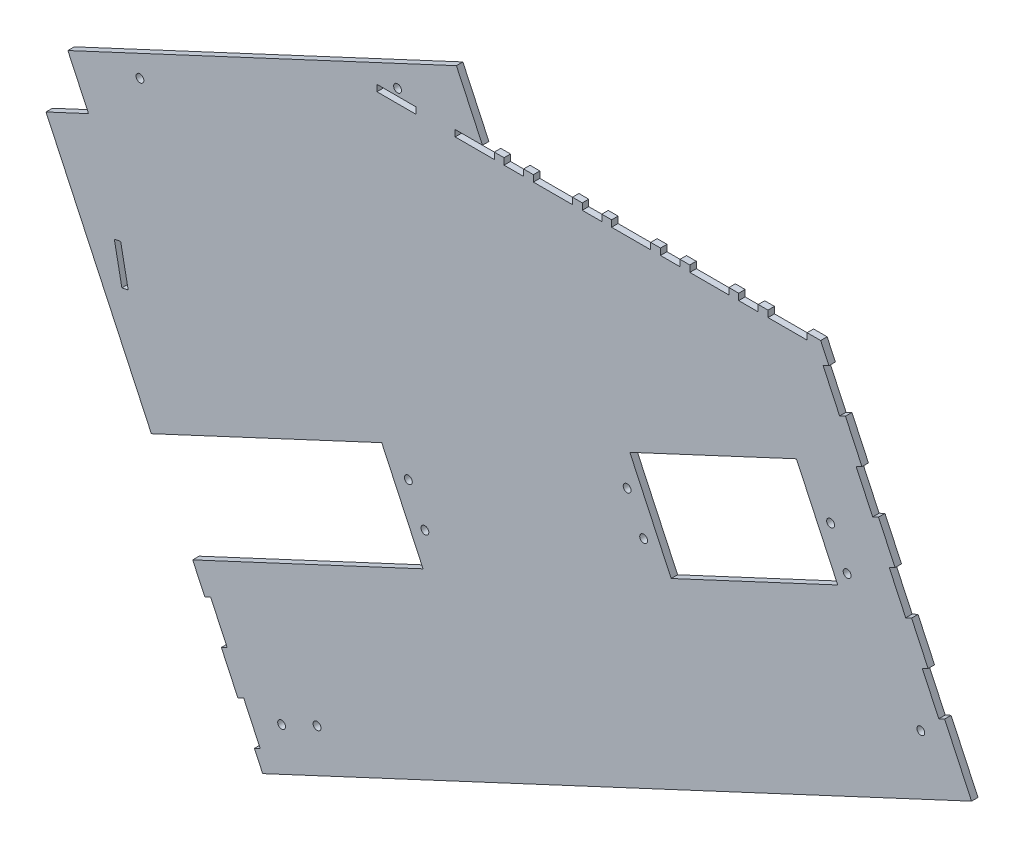
SolidWorks part; units mm, degrees
material "Balsa"
ref_plane "Front Plane" through (0, 0, 0) normal (0, 0, 1) x (1, 0, 0)
ref_plane "Top Plane" through (0, 0, 0) normal (0, 1, 0) x (1, 0, 0)
ref_plane "Right Plane" through (0, 0, 0) normal (1, 0, 0) x (0, 0, -1)
sketch "Sketch1" plane through (0, 0, 0) normal (0, 0, 1) x (1, 0, 0)
  line L0 (321.5462, 12.6346) -> (148.586, 12.6346)
  line L1 (148.586, 12.6346) -> (135.2566, 41.2196)
  line L2 (135.2566, 41.2196) -> (-63.4467, -51.4373)
  line L3 (-63.4467, -51.4373) -> (57.9293, -311.7289) construction
  line L4 (57.9293, -311.7289) -> (398.701, -152.8244)
  line L5 (271.5352, 119.8836) -> (277.3251, 107.4672) construction
  line L6 (190.5834, 136.311) -> (-12.0446, 41.824) construction
  line L7 (-63.4467, -51.4373) -> (255.5737, 97.3243) construction
  line L8 (398.701, -152.8244) -> (321.5462, 12.6346)
  line L9 (57.9293, -311.7289) -> (36.1779, -321.8717)
  line L10 (36.1779, -321.8717) -> (-74.6326, -84.2378)
  line L12 (-74.6326, -84.2378) -> (-52.8812, -74.095)
  line L13 (-90.9879, -49.1637) -> (-85.1981, -61.5801) construction
  line L14 (-52.8812, -74.095) -> (-63.4467, -51.4373)
  line L15 (73.956, 12.6346) -> (94.6178, 12.6346) construction
  line L19 (148.586, 12.6346) -> (135.2566, 41.2196) construction
  circle A0 centre (162.7613, -40.6644) radius 32.5 construction
  circle A1 centre (336.0773, -108.8767) radius 32.5 construction
  circle A2 centre (90.1802, -40.6644) radius 32.5 construction
  circle A3 centre (232.5481, -40.6644) radius 32.5 construction
  circle A4 centre (207.2768, 100.5118) radius 39.5 construction
  arc A5 (-3.3339, 41.4724) -> (-17.3744, 34.9252) centre (-8.0297, 33.2141) ccw construction
  circle A6 centre (304.5287, -40.6644) radius 32.5 construction
  circle A7 centre (254.9584, -108.8767) radius 32.5 construction
  circle A8 centre (179.3206, -108.8767) radius 32.5 construction
  circle A9 centre (101.4264, -108.8767) radius 32.5 construction
  circle A10 centre (270.383, -163.8108) radius 32.5 construction
  circle A11 centre (372.7594, -134.5783) radius 2
  dimension "D2" = 65
  dimension "D3" = 65
  dimension "D5" = 4
  dimension "D1" = 350
  dimension "D4" = 25
  dimension "24.5/2" = 15.8
  dimension "D6" = 27.5
extrude "Boss-Extrude1" add sketch "Sketch1" along normal up to surface (3.3 mm away)
sketch "Sketch2" plane through (0, 0, 3.3) normal (0, 0, 1) x (1, 0, 0)
  circle A0 centre (105.1447, 16.1444) radius 2
  circle A1 centre (-26.5934, -45.2861) radius 2
  circle A2 centre (-26.5934, -45.2861) radius 2 construction
  circle A3 centre (105.1447, 16.1444) radius 2 construction
extrude "Cut-Extrude1" cut sketch "Sketch2" against normal through all
sketch "Sketch3" plane through (0, 0, 3.3) normal (0, 0, 1) x (1, 0, 0)
  line L2 (398.701, -152.8244) -> (36.1779, -321.8717) construction
  line L3 (36.1779, -321.8717) -> (-74.6326, -84.2378) construction
  circle A0 centre (45.8517, -295.2932) radius 2
  circle A1 centre (63.9779, -286.8408) radius 2
  dimension "D1" = 4
  dimension "D2" = 4
  dimension "D3" = 20
  dimension "D5" = 20
  dimension "D6" = 20
  dimension "D4" = 20
extrude "Cut-Extrude2" cut sketch "Sketch3" against normal blind 4
sketch "Sketch4" plane through (0, 0, 3.3) normal (0, 0, 1) x (1, 0, 0)
  line L0 (330.2782, -91.2744) -> (309.1473, -45.959)
  line L1 (309.1473, -45.959) -> (223.9543, -85.6851)
  line L2 (223.9543, -85.6851) -> (245.0853, -131.0005)
  line L3 (245.0853, -131.0005) -> (330.2782, -91.2744)
  line L4 (309.1473, -45.959) -> (223.9543, -85.6851) construction
  line L5 (245.0853, -131.0005) -> (330.2782, -91.2744) construction
  line L6 (330.2782, -91.2744) -> (309.1473, -45.959) construction
  line L7 (118.2022, -190.1671) -> (97.0712, -144.8517)
  line L8 (97.0712, -144.8517) -> (-20.7488, -199.7921)
  line L9 (-20.7488, -199.7921) -> (0.3821, -245.1075)
  line L10 (0.3821, -245.1075) -> (118.2022, -190.1671)
  line L11 (118.2022, -190.1671) -> (0.3821, -245.1075) construction
  line L12 (-20.7488, -199.7921) -> (97.0712, -144.8517) construction
  line L13 (97.0712, -144.8517) -> (118.2022, -190.1671) construction
extrude "Cut-Extrude3" cut sketch "Sketch4" against normal blind 10
sketch "Sketch5" plane through (0, 0, 3.3) normal (0, 0, 1) x (1, 0, 0)
  circle A0 centre (231.009, -120.4069) radius 2
  circle A1 centre (222.5566, -102.2807) radius 2
  circle A2 centre (119.135, -172.5746) radius 2
  circle A3 centre (110.6826, -154.4484) radius 2
  circle A4 centre (119.135, -172.5746) radius 2 construction
  circle A7 centre (110.6826, -154.4484) radius 2 construction
  circle A8 centre (222.5566, -102.2807) radius 2 construction
  circle A9 centre (231.009, -120.4069) radius 2 construction
extrude "Cut-Extrude4" cut sketch "Sketch5" against normal blind 10
sketch "Sketch6" plane through (0, 0, 3.3) normal (0, 0, 1) x (1, 0, 0)
  line L0 (148.586, 12.6346) -> (321.5462, 12.6346) construction
  line L1 (314.6178, 12.6346) -> (294.6178, 12.6346)
  line L2 (314.6178, 12.6346) -> (314.6178, 9.3346)
  line L3 (314.6178, 9.3346) -> (294.6178, 9.3346)
  line L4 (294.6178, 12.6346) -> (294.6178, 9.3346)
  line L5 (314.6178, 12.6346) -> (294.6178, 9.3346) construction
  line L6 (314.6178, 9.3346) -> (294.6178, 12.6346) construction
  line L7 (314.6178, 9.3346) -> (314.6178, 12.6346) construction
  line L8 (274.6178, 9.3346) -> (254.6178, 9.3346)
  line L9 (254.6178, 12.6346) -> (254.6178, 9.3346)
  line L10 (274.6178, 12.6346) -> (274.6178, 9.3346)
  line L11 (274.6178, 12.6346) -> (254.6178, 12.6346)
  line L12 (234.6178, 9.3346) -> (214.6178, 9.3346)
  line L13 (214.6178, 12.6346) -> (214.6178, 9.3346)
  line L14 (234.6178, 12.6346) -> (234.6178, 9.3346)
  line L15 (234.6178, 12.6346) -> (214.6178, 12.6346)
  line L16 (194.6178, 9.3346) -> (174.6178, 9.3346)
  line L17 (174.6178, 12.6346) -> (174.6178, 9.3346)
  line L18 (194.6178, 12.6346) -> (194.6178, 9.3346)
  line L19 (194.6178, 12.6346) -> (174.6178, 12.6346)
  line L20 (154.6178, 9.3346) -> (134.6178, 9.3346)
  line L21 (134.6178, 12.6346) -> (134.6178, 9.3346)
  line L22 (154.6178, 12.6346) -> (154.6178, 9.3346)
  line L23 (154.6178, 12.6346) -> (134.6178, 12.6346)
  line L24 (114.6178, 9.3346) -> (94.6178, 9.3346)
  line L25 (94.6178, 12.6346) -> (94.6178, 9.3346)
  line L26 (114.6178, 12.6346) -> (114.6178, 9.3346)
  line L27 (114.6178, 12.6346) -> (94.6178, 12.6346)
  point P4 (304.6178, 10.9846)
  dimension "D1" = 3.3
  dimension "D2" = 20
  dimension "D3" = 6
extrude "Cut-Extrude5" cut sketch "Sketch6" against normal blind 10
sketch "Sketch7" plane through (0, 0, 3.3) normal (0, 0, 1) x (1, 0, 0)
  line L1 (325.7724, 3.5715) -> (322.7816, 2.1769)
  line L2 (325.7724, 3.5715) -> (334.2248, -14.5546)
  line L3 (334.2248, -14.5546) -> (331.2339, -15.9492)
  line L4 (322.7816, 2.1769) -> (331.2339, -15.9492)
  line L5 (325.7724, 3.5715) -> (331.2339, -15.9492) construction
  line L6 (334.2248, -14.5546) -> (322.7816, 2.1769) construction
  line L7 (322.7816, 2.1769) -> (331.2339, -15.9492) construction
  line L8 (334.2248, -14.5546) -> (342.6771, -32.6808) construction
  line L9 (331.2339, -15.9492) -> (334.2248, -14.5546) construction
  line L10 (321.5462, 12.6346) -> (398.701, -152.8244) construction
  line L11 (325.7724, 3.5715) -> (322.7816, 2.1769) construction
  line L12 (342.6771, -32.6808) -> (339.6863, -34.0754)
  line L13 (342.6771, -32.6808) -> (351.1295, -50.8069)
  line L14 (351.1295, -50.8069) -> (348.1387, -52.2016)
  line L15 (339.6863, -34.0754) -> (348.1387, -52.2016)
  line L16 (342.6771, -32.6808) -> (348.1387, -52.2016) construction
  line L17 (351.1295, -50.8069) -> (339.6863, -34.0754) construction
  line L18 (359.5819, -68.9331) -> (356.591, -70.3277)
  line L19 (359.5819, -68.9331) -> (368.0342, -87.0592)
  line L20 (368.0342, -87.0592) -> (365.0434, -88.4539)
  line L21 (356.591, -70.3277) -> (365.0434, -88.4539)
  line L22 (359.5819, -68.9331) -> (365.0434, -88.4539) construction
  line L23 (368.0342, -87.0592) -> (356.591, -70.3277) construction
  line L24 (376.4866, -105.1854) -> (373.4958, -106.58)
  line L25 (376.4866, -105.1854) -> (384.939, -123.3115)
  line L26 (384.939, -123.3115) -> (381.9481, -124.7062)
  line L27 (373.4958, -106.58) -> (381.9481, -124.7062)
  line L28 (376.4866, -105.1854) -> (381.9481, -124.7062) construction
  line L29 (384.939, -123.3115) -> (373.4958, -106.58) construction
  point P4 (330.6299, -10.0725)
  point P21 (347.5346, -46.3248)
  point P26 (364.4394, -82.5771)
  point P31 (381.3441, -118.8294)
  dimension "D1" = 4
extrude "Cut-Extrude6" cut sketch "Sketch7" against normal blind 10
sketch "Sketch8" plane through (0, 0, 3.3) normal (0, 0, 1) x (1, 0, 0)
  line L0 (148.586, 12.6346) -> (159.6178, 12.6346) construction
  line L1 (289.6178, 12.6346) -> (279.6178, 12.6346)
  line L2 (289.6178, 12.6346) -> (289.6178, 9.3346)
  line L3 (289.6178, 9.3346) -> (279.6178, 9.3346)
  line L4 (279.6178, 12.6346) -> (279.6178, 9.3346)
  line L5 (289.6178, 12.6346) -> (279.6178, 9.3346) construction
  line L6 (289.6178, 9.3346) -> (279.6178, 12.6346) construction
  line L7 (294.6178, 9.3346) -> (294.6178, 12.6346) construction
  line L8 (249.6178, 12.6346) -> (239.6178, 12.6346)
  line L9 (249.6178, 12.6346) -> (249.6178, 9.3346)
  line L10 (249.6178, 9.3346) -> (239.6178, 9.3346)
  line L11 (239.6178, 12.6346) -> (239.6178, 9.3346)
  line L12 (249.6178, 12.6346) -> (239.6178, 9.3346) construction
  line L13 (249.6178, 9.3346) -> (239.6178, 12.6346) construction
  line L14 (209.6178, 12.6346) -> (199.6178, 12.6346)
  line L15 (209.6178, 12.6346) -> (209.6178, 9.3346)
  line L16 (209.6178, 9.3346) -> (199.6178, 9.3346)
  line L17 (199.6178, 12.6346) -> (199.6178, 9.3346)
  line L18 (209.6178, 12.6346) -> (199.6178, 9.3346) construction
  line L19 (209.6178, 9.3346) -> (199.6178, 12.6346) construction
  line L20 (169.6178, 12.6346) -> (159.6178, 12.6346)
  line L21 (169.6178, 12.6346) -> (169.6178, 9.3346)
  line L22 (169.6178, 9.3346) -> (159.6178, 9.3346)
  line L23 (159.6178, 12.6346) -> (159.6178, 9.3346)
  line L24 (169.6178, 12.6346) -> (159.6178, 9.3346) construction
  line L25 (169.6178, 9.3346) -> (159.6178, 12.6346) construction
  point P4 (284.6178, 10.9846)
  point P14 (244.6178, 10.9846)
  point P19 (204.6178, 10.9846)
  point P24 (164.6178, 10.9846)
  dimension "D1" = 3.3
  dimension "D2" = 5
  dimension "D3" = 10
  dimension "D4" = 4
extrude "Cut-Extrude7" cut sketch "Sketch8" against normal blind 3.3
sketch "Sketch9" plane through (0, 0, 3.3) normal (0, 0, 1) x (1, 0, 0)
  line L0 (31.9517, -312.8086) -> (23.4994, -294.6825)
  line L1 (36.1779, -321.8717) -> (0.3821, -245.1075) construction
  line L2 (23.4994, -294.6825) -> (26.4902, -293.2878)
  line L3 (26.4902, -293.2878) -> (34.9425, -311.414)
  line L4 (34.9425, -311.414) -> (31.9517, -312.8086)
  line L5 (398.701, -152.8244) -> (36.1779, -321.8717) construction
  line L6 (15.047, -276.5563) -> (6.5946, -258.4302)
  line L7 (6.5946, -258.4302) -> (9.5855, -257.0355)
  line L8 (9.5855, -257.0355) -> (18.0378, -275.1617)
  line L9 (18.0378, -275.1617) -> (15.047, -276.5563)
  dimension "D1" = 3.3
  dimension "D2" = 20
  dimension "D3" = 10
  dimension "D4" = 2
extrude "Cut-Extrude8" cut sketch "Sketch9" against normal blind 3.3
sketch "Sketch10" plane through (0, 0, 3.3) normal (0, 0, 1) x (1, 0, 0)
  line L0 (-39.6914, -123.1134) -> (-35.8243, -142.7359)
  line L1 (-39.6914, -123.1134) -> (-36.4537, -122.4753)
  line L2 (-35.8243, -142.7359) -> (-32.5866, -142.0979)
  line L3 (-36.4537, -122.4753) -> (-32.5866, -142.0979)
  line L4 (-74.6326, -84.2378) -> (-52.8812, -74.095) construction
  line L5 (-44.9881, -96.237) -> (-39.6914, -123.1134) construction
  dimension "D1" = 20
  dimension "D2" = 50
  dimension "D3" = 3.3
extrude "Cut-Extrude9" cut sketch "Sketch10" against normal blind 3.3
sketch "Sketch11" plane through (0, 0, 3.3) normal (0, 0, 1) x (1, 0, 0)
  circle A0 centre (335.0681, -83.7998) radius 2
  circle A1 centre (326.6157, -65.6736) radius 2.0107
  circle A2 centre (335.0681, -83.7998) radius 2 construction
  circle A3 centre (326.6157, -65.6736) radius 2.0107 construction
extrude "Cut-Extrude10" cut sketch "Sketch11" against normal blind 10
